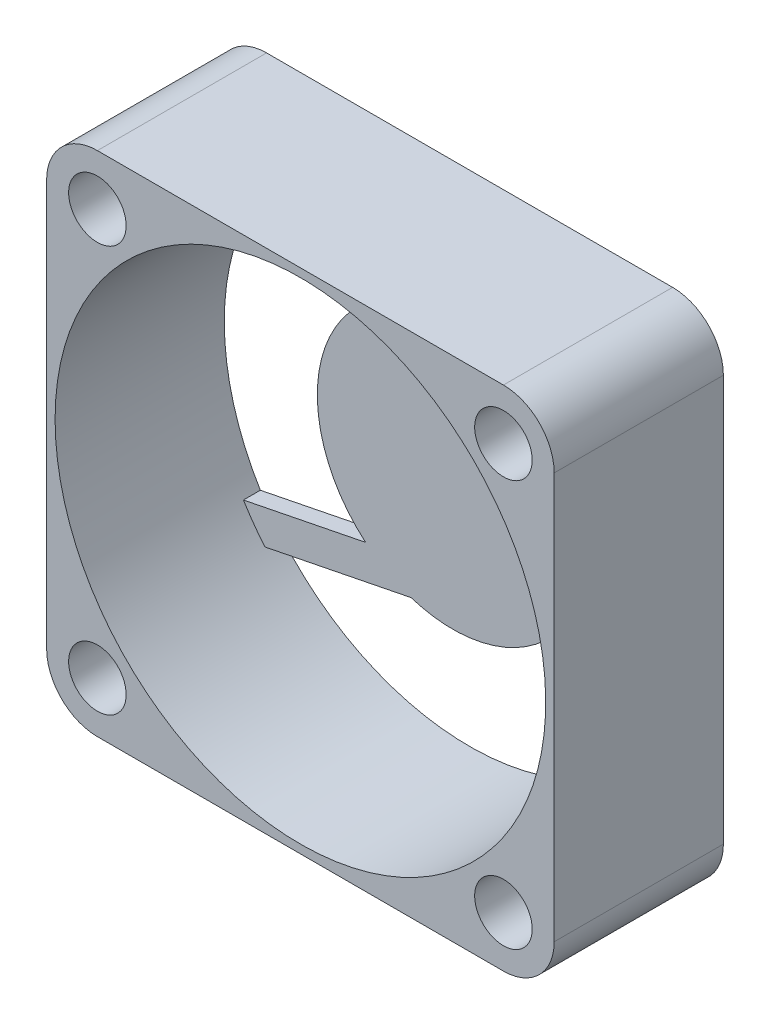
SolidWorks part; units mm, degrees
ref_plane "Plan de face" through (0, 0, 0) normal (0, 0, 1) x (1, 0, 0)
ref_plane "Plan de dessus" through (0, 0, 0) normal (0, 1, 0) x (1, 0, 0)
ref_plane "Plan de droite" through (0, 0, 0) normal (1, 0, 0) x (0, 0, -1)
ref_plane "Plan1" through (0, 0, 6.5) normal (0, 0, 1) x (1, 0, 0)
sketch "Esquisse1" plane through (0, 0, 6.5) normal (0, 0, 1) x (1, 0, 0)
  line L0 (6.4095, -4.7873) -> (12.0332, -8.0903)
  line L1 (-11.0939, -9.3367) -> (-2.4594, -7.6126)
  line L2 (12.9798, -6.4633) -> (7.3507, -3.1571)
  line L3 (0.9412, 7.9444) -> (0.9412, 14.4694)
  line L8 (-5.1437, -6.1272) -> (-12.3673, -7.5697)
  line L9 (-0.9482, 14.469) -> (-0.9482, 7.9436)
  line L11 (-12, -15) -> (12, -15)
  line L12 (-15, -12) -> (-15, 12)
  line L13 (-12, 15) -> (12, 15)
  line L14 (15, -12) -> (15, 12)
  line L15 (-15, -15) -> (15, 15) construction
  line L16 (-15, 15) -> (15, -15) construction
  arc A0 (12.0332, -8.0903) -> (-11.0939, -9.3367) centre (0, 0) cw
  arc A1 (-2.4594, -7.6126) -> (6.4095, -4.7873) centre (0, 0) ccw
  arc A2 (0.9412, 14.4694) -> (12.9798, -6.4633) centre (0, 0) cw
  arc A3 (7.3507, -3.1571) -> (0.9412, 7.9444) centre (0, 0) ccw
  arc A8 (-12.3673, -7.5697) -> (-0.9482, 14.469) centre (0, 0) cw
  arc A9 (-0.9482, 7.9436) -> (-5.1437, -6.1272) centre (0, 0) ccw
  arc A10 (-12, -15) -> (-15, -12) centre (-12, -12) cw
  arc A11 (12, -15) -> (15, -12) centre (12, -12) ccw
  arc A12 (12, 15) -> (15, 12) centre (12, 12) cw
  arc A13 (-15, 12) -> (-12, 15) centre (-12, 12) cw
  dimension "D3" = 3
  dimension "D1" = 14.5
  dimension "D4" = 8
  dimension "D2" = 30
extrude "Boss.-Extru.1" add sketch "Esquisse1" against normal blind 10
sketch "Esquisse2" plane through (0, 0, 6.5) normal (0, 0, 1) x (1, 0, 0)
  line L0 (-11.0939, -9.3367) -> (-2.4594, -7.6126)
  line L1 (6.4095, -4.7873) -> (12.0332, -8.0903)
  line L2 (12.9798, -6.4633) -> (7.3507, -3.1571)
  line L3 (0.9412, 7.9444) -> (0.9412, 14.4694)
  line L4 (-0.9482, 14.469) -> (-0.9482, 7.9436)
  line L5 (-5.1437, -6.1272) -> (-12.3673, -7.5697)
  arc A0 (-2.4594, -7.6126) -> (6.4095, -4.7873) centre (0, 0) ccw
  arc A1 (12.0332, -8.0903) -> (12.9798, -6.4633) centre (0, 0) ccw
  arc A2 (7.3507, -3.1571) -> (0.9412, 7.9444) centre (0, 0) ccw
  arc A3 (0.9412, 14.4694) -> (-0.9482, 14.469) centre (0, 0) ccw
  arc A4 (-0.9482, 7.9436) -> (-5.1437, -6.1272) centre (0, 0) ccw
  arc A5 (-12.3673, -7.5697) -> (-11.0939, -9.3367) centre (0, 0) ccw
extrude "Enlèv. mat.-Extru.1" cut sketch "Esquisse2" against normal offset from surface (9 mm away) 1 up to face at (-7.5612, 3.3286, -3.5)
sketch "Esquisse3" plane through (0, 0, 6.5) normal (0, 0, 1) x (1, 0, 0)
  line L5 (-12, -15) -> (12, -15) construction
  line L6 (-12, -12) -> (12, -12) construction
  line L7 (-12, -12) -> (-12, 12) construction
  line L8 (-12, 12) -> (12, 12) construction
  line L9 (12, -12) -> (12, 12) construction
  line L10 (-12, -12) -> (12, 12) construction
  line L11 (-12, 12) -> (12, -12) construction
  point P0 (0, 0)
  point P15 (0, 0)
  dimension "D1" = 24
hole_wizard "Dégagement M32" positions "Esquisse5" profile "Esquisse4" hole size "M3" standard "ISO" end condition through all
sketch "Esquisse5" plane through (0, 0, 6.5) normal (0, 0, 1) x (1, 0, 0)
  point P0 (-12, 12)
  point P3 (-12, -12)
  point P6 (12, -12)
  point P9 (12, 12)
sketch "Esquisse4" plane through (-12, 12, 6.5) normal (1, 0, 0) x (0, -1, 0)
  line L0 (0, 0) -> (0, 10)
  line L1 (0, 10) -> (1.7, 10)
  line L2 (1.7, 10) -> (1.7, 0)
  line L5 (1.7, 0) -> (0, 0)
  line L11 (0, -6.35) -> (0, 107.95) construction
  dimension "Diamètre du perçage jusqu'au prochain" = 3.4
  dimension "Profondeur du perçage jusqu'au prochain" = 10
ref_axis "Axe1" through (0, 0, -3.5) along (0, 0, 1)
